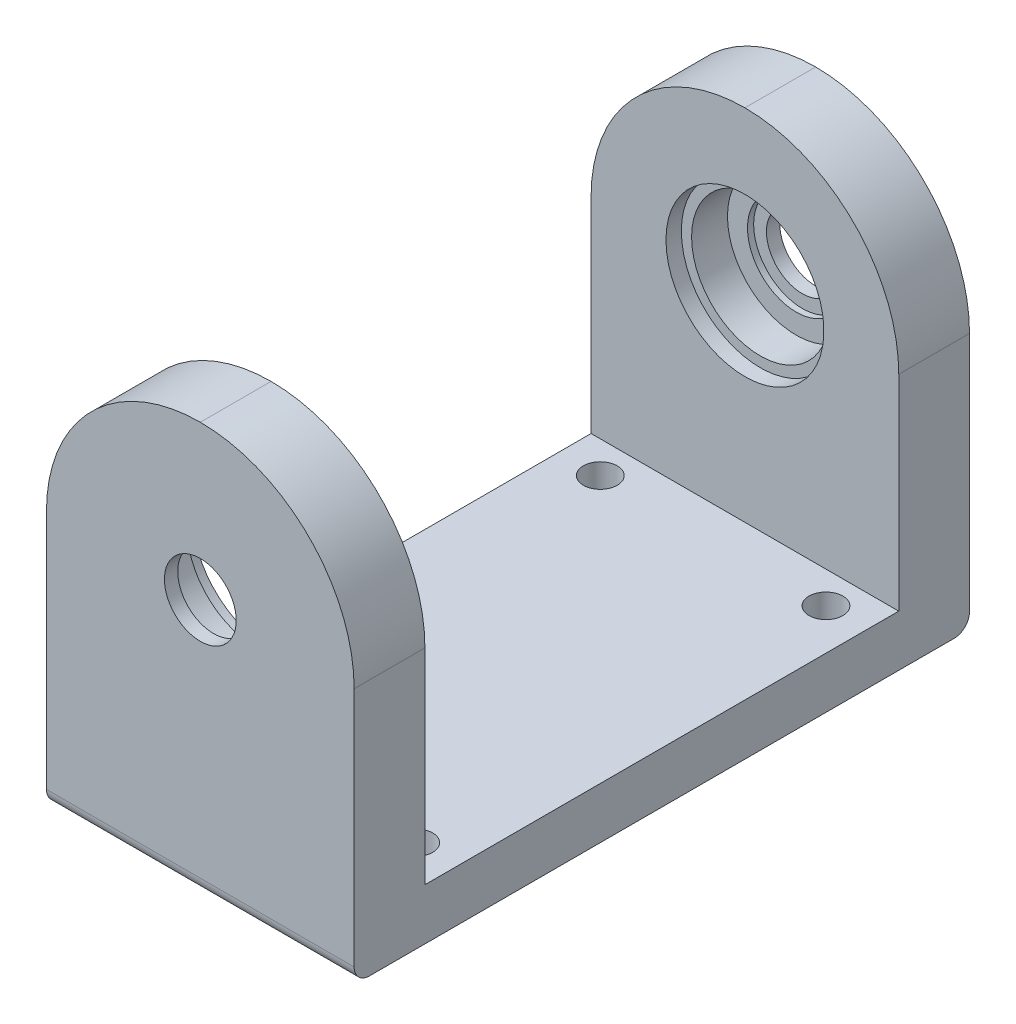
SolidWorks part; units mm, degrees
ref_plane "Front Plane" through (0, 0, 0) normal (0, 0, 1) x (1, 0, 0)
ref_plane "Top Plane" through (0, 0, 0) normal (0, 1, 0) x (1, 0, 0)
ref_plane "Right Plane" through (0, 0, 0) normal (1, 0, 0) x (0, 0, -1)
sketch "Sketch1" plane through (0, 0, 0) normal (0, 1, 0) x (1, 0, 0)
  line L0 (-1.3042, 0) -> (2.0884, 0) construction
  line L1 (0, 5.5134) -> (0, -5.3226) construction
  line L2 (15, 20) -> (-15, 20) construction
  line L3 (15, -30) -> (-15, -30)
  line L4 (15, -30) -> (15, 30)
  line L5 (15, 30) -> (-15, 30)
  line L6 (-15, -30) -> (-15, 30)
  line L7 (15, -30) -> (-15, 30) construction
  line L8 (15, 30) -> (-15, -30) construction
  line L9 (15, -20) -> (-15, -20) construction
  point P4 (0, 0)
  dimension "D1" = 10
  dimension "D2" = 60
  dimension "D3" = 30
extrude "Boss-Extrude1" add sketch "Sketch1" along normal blind 5
ref_plane "Plane1" through (0, 0, 30) normal (0, 0, 1) x (1, 0, 0)
sketch "Sketch3" plane through (0, 0, 30) normal (0, 0, 1) x (1, 0, 0)
  line L0 (-15, 5) -> (15, 5)
  line L1 (15, 5) -> (15, 0) construction
  line L2 (-15, 5) -> (15, 5) construction
  line L3 (15, 5) -> (15, 25)
  line L4 (-15, 5) -> (-15, 25)
  line L5 (-15, 25) -> (-15, 40)
  line L6 (15, 25) -> (15, 40)
  line L7 (15, 40) -> (-15, 40)
  circle A1 centre (0, 25) radius 3.5
  circle A2 centre (0, 25) radius 22.5 construction
  dimension "D1" = 7
  dimension "D3" = 45
  dimension "D2" = 25
  dimension "D4" = 15
extrude "Boss-Extrude2" add sketch "Sketch3" against normal blind 6.9
sketch "Sketch4" plane through (0, 0, 23.1) normal (0, 0, -1) x (-1, 0, 0)
  line L0 (0, 0) -> (0, 40) construction
  line L1 (-15, 0) -> (15, 0) construction
  line L2 (-15, 40) -> (15, 40) construction
  circle A1 centre (0, 25) radius 7.7
  dimension "D1" = 15.4
extrude "Cut-Extrude1" cut sketch "Sketch4" against normal blind 1.5
sketch "Sketch6" plane through (0, 0, 24.6) normal (0, 0, -1) x (-1, 0, 0)
  circle A1 centre (0, 25) radius 6.7
  dimension "D1" = 13.4
extrude "Cut-Extrude2" cut sketch "Sketch6" against normal blind 3.5
sketch "Sketch9" plane through (0, 0, 28.1) normal (0, 0, -1) x (-1, 0, 0)
  circle A1 centre (0, 25) radius 4.75
  dimension "D1" = 9.5
extrude "Cut-Extrude4" cut sketch "Sketch9" against normal blind 0.6
mirror "Mirror2" about plane through (0, 0, 0) normal (0, 0, 1) of "Cut-Extrude4", "Boss-Extrude2", "Cut-Extrude1", "Cut-Extrude2"
fillet "Fillet1" radius 15 4 edges at (15, 40, -26.55) (-15, 40, -26.55) (-15, 40, 26.55) (15, 40, 26.55)
sketch "Sketch15" plane through (0, 5, 0) normal (0, 1, 0) x (1, 0, 0)
  line L0 (0, 23.1) -> (0, -23.1) construction
  line L1 (-15, 23.1) -> (15, 23.1) construction
  line L2 (-15, -20) -> (15, -20) construction
  line L3 (-15, 23.1) -> (-15, -23.1) construction
  line L4 (15, -23.1) -> (15, 23.1) construction
  line L5 (-15, 20) -> (15, 20) construction
  line L6 (0, 30) -> (-15, 30) construction
  line L7 (-15, -30) -> (0, -30) construction
  line L8 (-15, 23.1) -> (-15, 30) construction
  line L9 (15, 30) -> (15, 23.1) construction
  circle A0 centre (-11, -20) radius 1.65
  circle A1 centre (11, -20) radius 1.65
  circle A2 centre (-11, 20) radius 1.65
  circle A3 centre (11, 20) radius 1.65
  point P25 (0, 0)
  point P26 (0, 0)
  dimension "D3" = 3.3
  dimension "D1" = 10
  dimension "D2" = 10
  dimension "D4" = 4
  dimension "D5" = 4
extrude "Cut-Extrude5" cut sketch "Sketch15" against normal blind 10
sketch "Sketch16" plane through (0, 0, 0) normal (0, -1, 0) x (1, 0, 0)
  line L0 (-15, 20) -> (15, 20) construction
  line L1 (-15, -30) -> (-15, 30) construction
  line L2 (15, 30) -> (15, -30) construction
  line L3 (-15, -20) -> (15, -20) construction
  line L5 (-7.5, 16.875) -> (7.5, 16.875)
  line L6 (-7.5, 16.875) -> (-7.5, 23.125)
  line L7 (-7.5, 23.125) -> (7.5, 23.125)
  line L8 (7.5, 16.875) -> (7.5, 23.125)
  line L9 (-7.5, 16.875) -> (7.5, 23.125) construction
  line L10 (-7.5, 23.125) -> (7.5, 16.875) construction
  line L11 (-7.5, -23.125) -> (7.5, -23.125)
  line L12 (-7.5, -23.125) -> (-7.5, -16.875)
  line L13 (-7.5, -16.875) -> (7.5, -16.875)
  line L14 (7.5, -23.125) -> (7.5, -16.875)
  line L15 (-7.5, -23.125) -> (7.5, -16.875) construction
  line L16 (-7.5, -16.875) -> (7.5, -23.125) construction
  point P10 (0, 20)
  point P15 (0, -20)
  dimension "D1" = 6.25
  dimension "D2" = 15
extrude "Boss-Extrude3" add sketch "Sketch16" along normal blind 5
fillet "Fillet2" radius 1.5 2 edges at (0, 0, -30) (0, 0, 30)
fillet "Fillet3" radius 1 4 edges at (0, -5, 23.125) (0, -5, 16.875) (0, -5, -16.875) (0, -5, -23.125)
